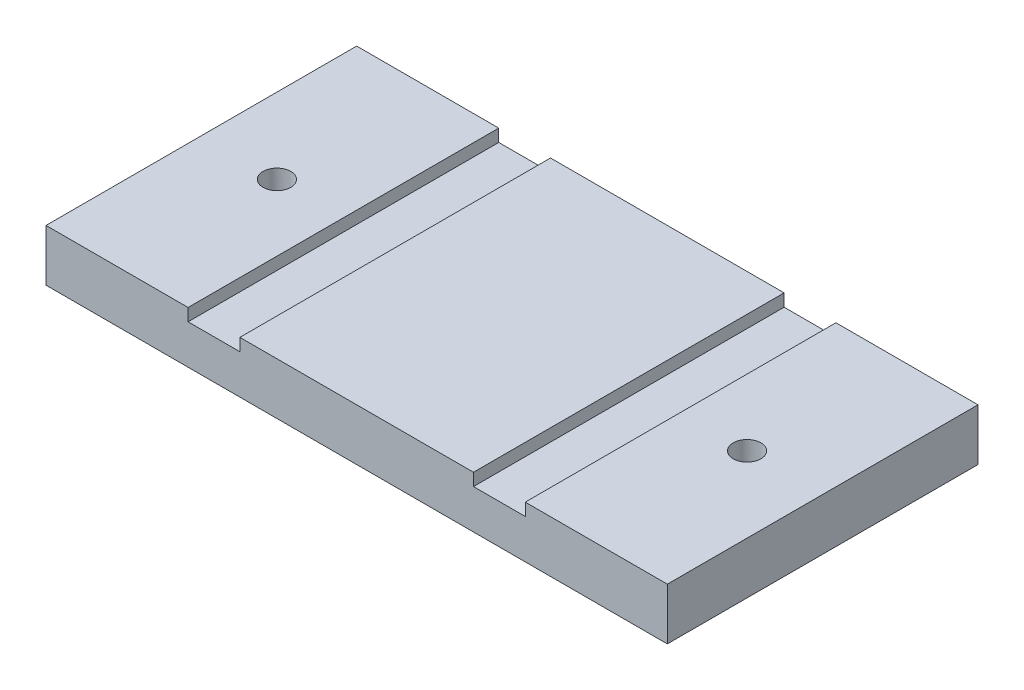
SolidWorks part; units mm, degrees
material "Delrin 2700 NC010, Low Viscosity Acetal Copolymer (SS)"
ref_plane "Front Plane" through (0, 0, 0) normal (0, 0, 1) x (1, 0, 0)
ref_plane "Top Plane" through (0, 0, 0) normal (0, 1, 0) x (1, 0, 0)
ref_plane "Right Plane" through (0, 0, 0) normal (1, 0, 0) x (0, 0, -1)
sketch "Sketch1" plane through (0, 0, 0) normal (0, 1, 0) x (1, 0, 0)
  line L1 (0, 0) -> (76.2, 0)
  line L2 (0, 0) -> (0, 38.1)
  line L3 (0, 38.1) -> (76.2, 38.1)
  line L4 (76.2, 0) -> (76.2, 38.1)
  dimension "D1" = 76.2
  dimension "D2" = 38.1
extrude "Boss-Extrude1" add sketch "Sketch1" along normal blind 6.35
hole_wizard "M3 Clearance Hole1" positions "Sketch4" profile "Sketch3" hole size "M3" standard "ANSI Metric" end condition through all
sketch "Sketch4" plane through (0, 6.35, 0) normal (0, 1, 0) x (1, 0, 0)
  line L0 (0, 19.05) -> (76.2, 19.05) construction
  line L1 (0, 38.1) -> (0, 0) construction
  line L2 (76.2, 0) -> (76.2, 38.1) construction
  line L4 (38.1, 0) -> (38.1, 38.1) construction
  line L5 (0, 0) -> (76.2, 0) construction
  line L6 (76.2, 38.1) -> (0, 38.1) construction
  point P0 (9.271, 19.05)
  point P2 (66.929, 19.05)
  point P22 (0, 0)
  dimension "D1" = 28.829
  dimension "D2" = 28.829
sketch "Sketch3" plane through (9.271, 6.35, -19.05) normal (1, 0, 0) x (0, 0, 1)
  line L0 (0, 0) -> (0, 6.35)
  line L1 (0, 6.35) -> (1.7, 6.35)
  line L2 (1.7, 6.35) -> (1.7, 0)
  line L5 (1.7, 0) -> (0, 0)
  line L11 (0, -6.35) -> (0, 107.95) construction
  dimension "Thru Hole Dia." = 3.4
  dimension "Thru Hole Depth" = 6.35
sketch "Sketch5" plane through (0, 0, 0) normal (0, 0, 1) x (1, 0, 0)
  line L0 (38.1, 6.35) -> (38.1, 0) construction
  line L5 (0, 6.35) -> (76.2, 6.35) construction
  line L6 (0, 0) -> (76.2, 0) construction
  line L7 (58.775, 4.826) -> (52.425, 4.826)
  line L8 (17.425, 6.35) -> (23.775, 6.35)
  line L9 (17.425, 6.35) -> (17.425, 4.826)
  line L10 (17.425, 4.826) -> (23.775, 4.826)
  line L11 (23.775, 6.35) -> (23.775, 4.826)
  line L12 (52.425, 6.35) -> (52.425, 4.826)
  line L13 (58.775, 6.35) -> (52.425, 6.35)
  line L14 (58.775, 6.35) -> (58.775, 4.826)
  point P11 (20.6, 4.826)
  dimension "D1" = 6.35
  dimension "D2" = 17.5
  dimension "D3" = 1.524
extrude "Cut-Extrude1" cut sketch "Sketch5" against normal through all
equation "\"spool lenght\"= 45mm"
equation "\"hole distance\"= 0.25in"
equation "\"D2@Sketch4\"=\"spool lenght\"/2 + \"hole distance\""
equation "\"D1@Sketch4\"=\"spool lenght\"/2 + \"hole distance\""
equation "\"tooth clearance\"= 1.5mm"
equation "\"D3@Sketch5\"=\"tooth clearance\""
